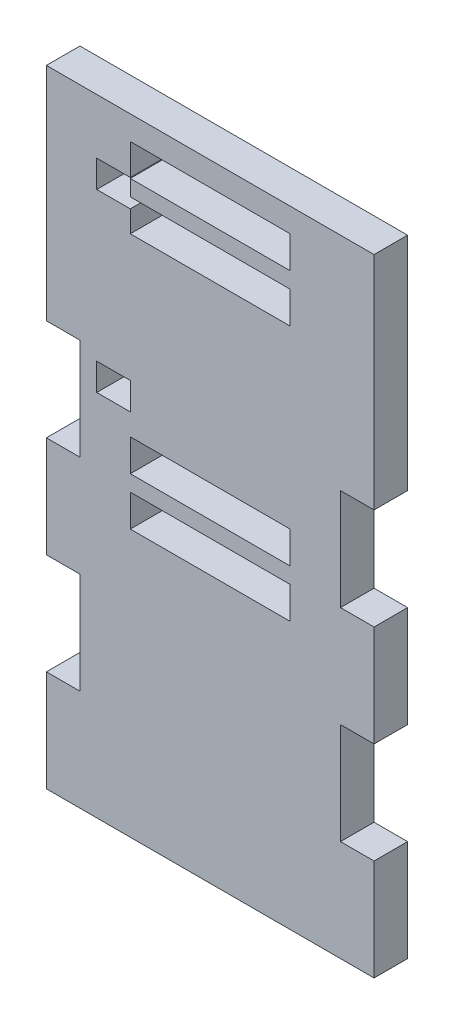
SolidWorks part; units mm, degrees
ref_plane "Front Plane" through (0, 0, 0) normal (0, 0, 1) x (1, 0, 0)
ref_plane "Top Plane" through (0, 0, 0) normal (0, 1, 0) x (1, 0, 0)
ref_plane "Right Plane" through (0, 0, 0) normal (1, 0, 0) x (0, 0, -1)
sketch "Sketch1" plane through (0, 0, 0) normal (0, 0, 1) x (1, 0, 0)
  line L1 (-38.9473, 40.8312) -> (13.1227, 40.8312)
  line L2 (-38.9473, 40.8312) -> (-38.9473, -39.6868)
  line L3 (-38.9473, -39.6868) -> (13.1227, -39.6868)
  line L4 (13.1227, 40.8312) -> (13.1227, -39.6868)
  dimension "D1" = 80.518
  dimension "D2" = 52.07
extrude "Boss-Extrude1" add sketch "Sketch1" along normal blind 5.334
sketch "Sketch2" plane through (0, 0, 5.334) normal (0, 0, 1) x (1, 0, 0)
  line L0 (-38.9473, 40.8312) -> (-38.9473, -39.6868) construction
  line L1 (-38.9473, 24.7276) -> (-33.6133, 24.7276)
  line L2 (-38.9473, 24.7276) -> (-38.9473, 8.624)
  line L3 (-38.9473, 8.624) -> (-33.6133, 8.624)
  line L4 (-33.6133, 24.7276) -> (-33.6133, 8.624)
  line L5 (-33.6133, 24.7276) -> (-33.6133, 40.8312) construction
  line L6 (-38.9473, -7.4796) -> (-33.6133, -7.4796)
  line L7 (-38.9473, -7.4796) -> (-38.9473, -23.5832)
  line L8 (-38.9473, -23.5832) -> (-33.6133, -23.5832)
  line L9 (-33.6133, -7.4796) -> (-33.6133, -23.5832)
  line L10 (13.1227, 40.8312) -> (-38.9473, 40.8312) construction
  line L11 (-33.6133, 8.624) -> (-33.6133, -7.4796) construction
  line L12 (-33.6133, -7.4796) -> (-33.9376, -7.3715) construction
  line L13 (-33.6133, -23.5832) -> (-33.6133, -39.6868) construction
  line L14 (-38.9473, -39.6868) -> (13.1227, -39.6868) construction
  line L15 (-12.9123, 40.8312) -> (-12.9123, -39.6868) construction
  line L16 (7.7887, -23.5832) -> (7.7887, -39.6868) construction
  line L17 (7.7887, -7.4796) -> (8.113, -7.3715) construction
  line L18 (7.7887, 8.624) -> (7.7887, -7.4796) construction
  line L19 (7.7887, 24.7276) -> (7.7887, 40.8312) construction
  line L20 (7.7887, -7.4796) -> (7.7887, -23.5832)
  line L21 (13.1227, -23.5832) -> (7.7887, -23.5832)
  line L22 (13.1227, -7.4796) -> (13.1227, -23.5832)
  line L23 (13.1227, -7.4796) -> (7.7887, -7.4796)
  line L24 (7.7887, 24.7276) -> (7.7887, 8.624)
  line L25 (13.1227, 8.624) -> (7.7887, 8.624)
  line L26 (13.1227, 24.7276) -> (13.1227, 8.624)
  line L27 (13.1227, 24.7276) -> (7.7887, 24.7276)
  dimension "D1" = 5.334
extrude "Cut-Extrude1" cut sketch "Sketch2" against normal through all
sketch "Sketch4" plane through (0, 0, 5.334) normal (0, 0, 1) x (1, 0, 0)
  line L0 (13.1227, 24.7276) -> (13.1227, 40.8312) construction
  line L1 (-38.9473, 24.7276) -> (13.1227, 24.7276)
  line L2 (-38.9473, 24.7276) -> (-38.9473, 59.8812)
  line L3 (-38.9473, 59.8812) -> (13.1227, 59.8812)
  line L4 (13.1227, 24.7276) -> (13.1227, 59.8812)
  line L5 (13.1227, 40.8312) -> (-38.9473, 40.8312) construction
  dimension "D1" = 0
  dimension "D2" = 19.05
extrude "Boss-Extrude2" add sketch "Sketch4" against normal blind 5.334
sketch "Sketch5" plane through (0, 0, 5.334) normal (0, 0, 1) x (1, 0, 0)
  line L0 (-12.9123, 59.8812) -> (-12.9123, -39.6868) construction
  line L1 (13.1227, 59.8812) -> (-38.9473, 59.8812) construction
  line L2 (-38.9473, -39.6868) -> (13.1227, -39.6868) construction
  line L3 (-25.6123, 15.4312) -> (-0.2123, 15.4312)
  line L4 (-25.6123, 56.0712) -> (-0.2123, 56.0712)
  line L5 (-25.6123, 56.0712) -> (-25.6123, 50.9912)
  line L6 (-25.6123, 50.9912) -> (-0.2123, 50.9912)
  line L7 (-0.2123, 56.0712) -> (-0.2123, 50.9912)
  line L8 (-25.6123, 10.3512) -> (-0.2123, 10.3512)
  line L9 (-25.6123, 15.4312) -> (-25.6123, 10.3512)
  line L10 (-0.2123, 15.4312) -> (-0.2123, 10.3512)
  line L11 (-25.6123, 48.4512) -> (-0.2123, 48.4512)
  line L12 (-25.6123, 43.3712) -> (-0.2123, 43.3712)
  line L13 (-25.6123, 48.4512) -> (-25.6123, 43.3712)
  line L14 (-0.2123, 48.4512) -> (-0.2123, 43.3712)
  line L19 (-25.6123, 7.8112) -> (-0.2123, 7.8112)
  line L20 (-25.6123, 2.7312) -> (-0.2123, 2.7312)
  line L21 (-25.6123, 7.8112) -> (-25.6123, 2.7312)
  line L22 (-0.2123, 7.8112) -> (-0.2123, 2.7312)
  dimension "D1" = 5.08
  dimension "D2" = 12.7
  dimension "D3" = 25.4
  dimension "D4" = 3.81
  dimension "D5" = 2
  dimension "D6" = 2
  dimension "D8" = 2
extrude "Cut-Extrude5" cut sketch "Sketch5" against normal through all
sketch "Sketch6" plane through (0, 0, 5.334) normal (0, 0, 1) x (1, 0, 0)
  line L0 (-25.6123, 51.1182) -> (-25.6123, 23.1782) construction
  line L1 (-30.9463, 46.8002) -> (-25.6123, 46.8002)
  line L2 (-30.9463, 46.8002) -> (-30.9463, 51.1182)
  line L3 (-30.9463, 51.1182) -> (-25.6123, 51.1182)
  line L4 (-25.6123, 46.8002) -> (-25.6123, 51.1182)
  line L5 (-30.9463, 23.1782) -> (-25.6123, 23.1782)
  line L6 (-30.9463, 23.1782) -> (-30.9463, 18.8602)
  line L7 (-30.9463, 18.8602) -> (-25.6123, 18.8602)
  line L8 (-25.6123, 23.1782) -> (-25.6123, 18.8602)
  line L9 (-30.9463, 51.1182) -> (-30.9463, 23.1782) construction
  line L11 (-25.6123, 48.4512) -> (-25.6123, 43.3712) construction
  line L14 (-25.6123, 43.3712) -> (-0.2123, 43.3712) construction
  dimension "D1" = 4.318
  dimension "D3" = 4.318
  dimension "D4" = 5.334
  dimension "D6" = 0
  dimension "D2" = 23.622
  dimension "D5" = 7.747
extrude "Cut-Extrude6" cut sketch "Sketch6" against normal through all
equation "\"MDF\"= .21in"
equation "\"Foamcore\"= .13in"
equation "\"Gmaterial\"= \"MDF\""
equation "\"D2@Sketch1\"=2*\"MDF\"+1.63"
equation "\"D1@Boss-Extrude1\"=\"MDF\""
equation "\"D1@Sketch2\"=\"MDF\""
equation "\"D4@Sketch6\"=\"MDF\""
